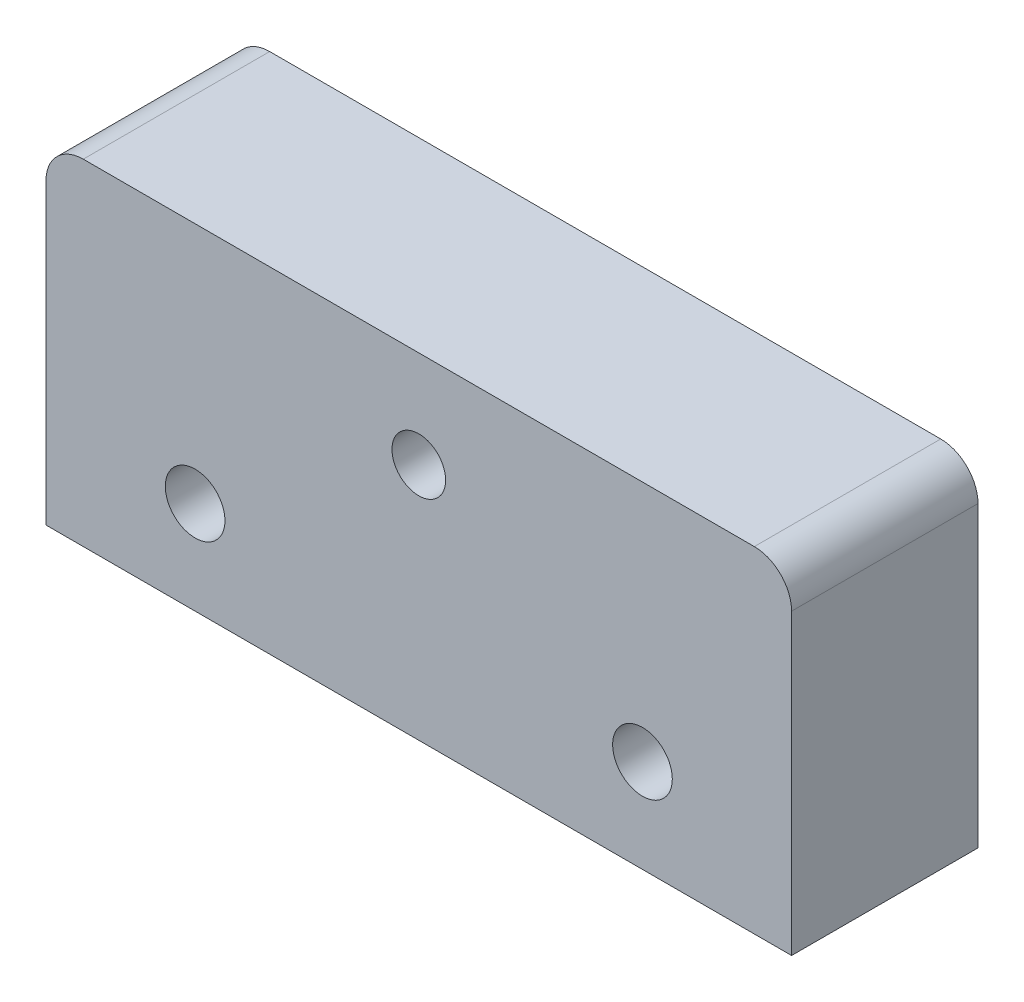
SolidWorks part; units mm, degrees
ref_plane "Front Plane" through (0, 0, 0) normal (0, 0, 1) x (1, 0, 0)
ref_plane "Top Plane" through (0, 0, 0) normal (0, 1, 0) x (1, 0, 0)
ref_plane "Right Plane" through (0, 0, 0) normal (1, 0, 0) x (0, 0, -1)
sketch "Sketch1" plane through (0, 0, 0) normal (0, 0, 1) x (1, 0, 0)
  line L0 (0, 0) -> (100, 0)
  line L1 (100, 0) -> (100, 45)
  line L2 (100, 45) -> (0, 45)
  line L3 (0, 45) -> (0, 0)
  line L4 (100, 12.5) -> (0, 12.5) construction
  line L5 (50, 25) -> (50, 45) construction
  line L6 (100, 45) -> (99.7108, 45.2871)
  line L7 (0, 25) -> (100, 25) construction
  circle A0 centre (20, 12.5) radius 4
  circle A1 centre (50, 32) radius 3.6
  circle A2 centre (80, 12.5) radius 7
  circle A3 centre (80, 12.5) radius 4
  circle A4 centre (50, 32) radius 11
  circle A5 centre (20, 12.5) radius 7
  dimension "D3" = 8
  dimension "D6" = 22
  dimension "D8" = 7.2
  dimension "D11" = 14
  dimension "D1" = 100
  dimension "D2" = 45
  dimension "D4" = 7
  dimension "D5" = 12.5
  dimension "D7" = 25
  dimension "D9" = 20
  dimension "D10" = 20
extrude "Boss-Extrude1" add sketch "Sketch1" along normal blind 25 contours L2 L3 L0 L1 A4 A3 A0 | A4 A1 | A2 A3 | A5 A0 region at (1.0966, 22.5, 0) region at (73.198, 12.5, 0) region at (39.3111, 32, 0) region at (13.198, 12.5, 0)
extrude "Cut-Extrude1" cut sketch "Sketch1<3>" along normal blind 7.5 contours A4
sketch "Sketch1<3>" plane through (0, 0, 0) normal (0, 0, 1) x (1, 0, 0) same geometry as "Sketch1"
fillet "Fillet1" radius 5 2 edges at (100, 45, 12.5) (0, 45, 12.5)
extrude "Cut-Extrude2" cut sketch "Sketch1<4>" along normal blind 8 contours A2 | A5
sketch "Sketch1<4>" plane through (0, 0, 0) normal (0, 0, 1) x (1, 0, 0) same geometry as "Sketch1"
